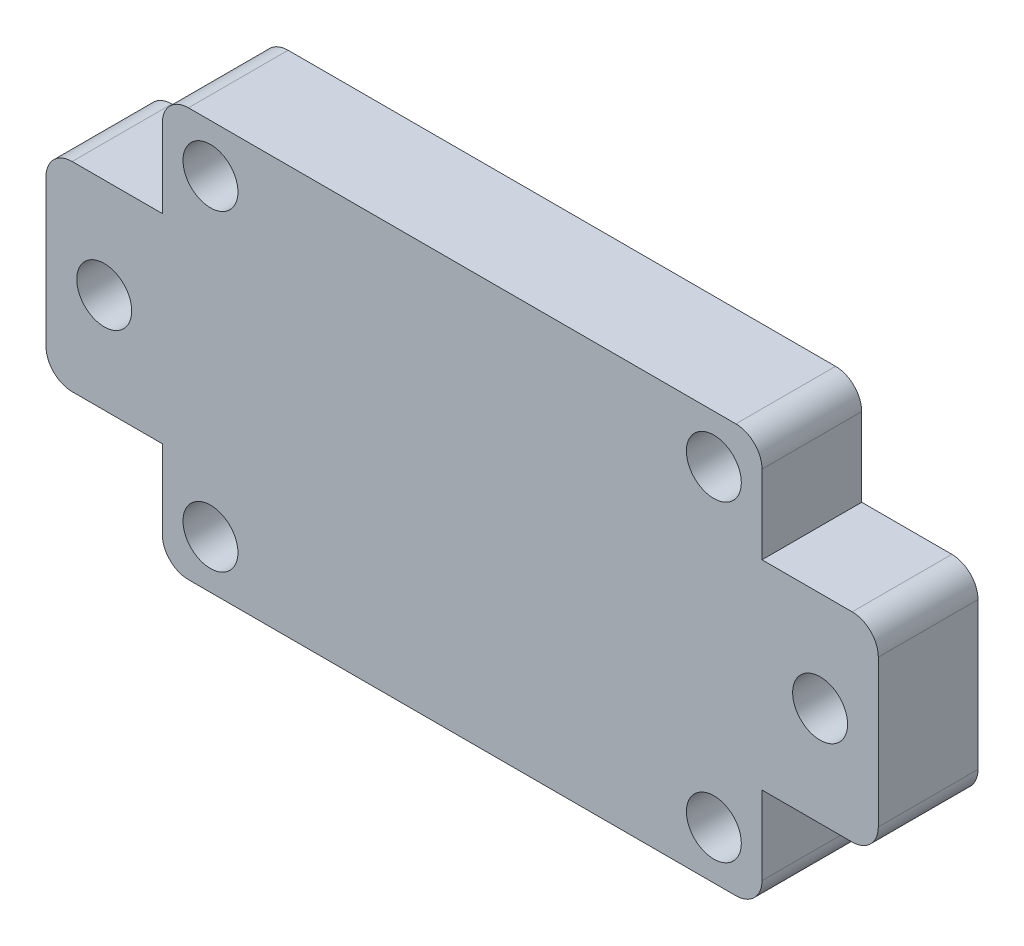
SolidWorks part; units mm, degrees
material "Custom Plastic"
ref_plane "X-Y Datum" through (0, 0, 0) normal (0, 0, 1) x (1, 0, 0)
ref_plane "X-Z Datum" through (0, 0, 0) normal (0, 1, 0) x (1, 0, 0)
ref_plane "Y-Z Datum" through (0, 0, 0) normal (1, 0, 0) x (0, 0, -1)
sketch "Sketch2" plane through (0, 0, -0.4115) normal (0, 0, -1) x (-1, 0, 0)
  line L0 (-92.964, 58.674) -> (-92.964, 50.673)
  line L1 (-138.811, 81.915) -> (-92.964, 81.915)
  line L2 (-138.811, 81.915) -> (-138.811, 73.914)
  line L3 (-138.811, 50.673) -> (-92.964, 50.673)
  line L4 (-92.964, 81.915) -> (-92.964, 73.914)
  line L6 (-84.074, 66.294) -> (-84.074, 73.914)
  line L7 (-84.074, 73.914) -> (-92.964, 73.914)
  line L8 (-84.074, 66.294) -> (-84.074, 58.674)
  line L9 (-84.074, 58.674) -> (-92.964, 58.674)
  line L11 (-147.701, 58.674) -> (-138.811, 58.674)
  line L12 (-147.701, 66.294) -> (-147.701, 58.674)
  line L13 (-147.701, 66.294) -> (-147.701, 73.914)
  line L14 (-147.701, 73.914) -> (-138.811, 73.914)
  line L15 (-138.811, 58.674) -> (-138.811, 50.673)
  dimension "D1" = 8.89
  dimension "D2" = 15.24
extrude "Boss-Extrude1" add sketch "Sketch2" along normal blind 7.62
sketch "Sketch3" plane through (0, 0, -0.4115) normal (0, 0, 1) x (1, 0, 0)
  line L0 (84.074, 58.674) -> (84.074, 73.914) construction
  line L1 (147.701, 73.914) -> (147.701, 58.674) construction
  circle A0 centre (96.647, 78.232) radius 2.1
  circle A1 centre (135.128, 78.232) radius 2.1
  circle A2 centre (135.128, 54.356) radius 2.1
  circle A3 centre (96.647, 54.356) radius 2.1
  circle A4 centre (88.524, 66.294) radius 2.1
  circle A5 centre (143.251, 66.294) radius 2.1
  dimension "D1" = 4.2
  dimension "D2" = 4.2
  dimension "D4" = 4.2
  dimension "D3" = 4.45
  dimension "D5" = 4.45
extrude "Cut-Extrude1" cut sketch "Sketch3" against normal through all contours A4 | A5 region at (88.524, 66.294, -0.4115) region at (143.251, 66.294, -0.4115)
extrude "Cut-Extrude2" cut sketch "Sketch3<3>" against normal blind 6.35 contours A0 | A3 | A2 | A1 region at (96.647, 78.232, -0.4115)
sketch "Sketch3<3>" plane through (0, 0, -0.4115) normal (0, 0, 1) x (1, 0, 0) same geometry as "Sketch3"
fillet "Fillet1" radius 2 8 edges at (147.701, 58.674, -4.2215) (147.701, 73.914, -4.2215) (138.811, 81.915, -4.2215) (138.811, 50.673, -4.2215) (92.964, 81.915, -4.2215) (84.074, 73.914, -4.2215) (92.964, 50.673, -4.2215) (84.074, 58.674, -4.2215)
